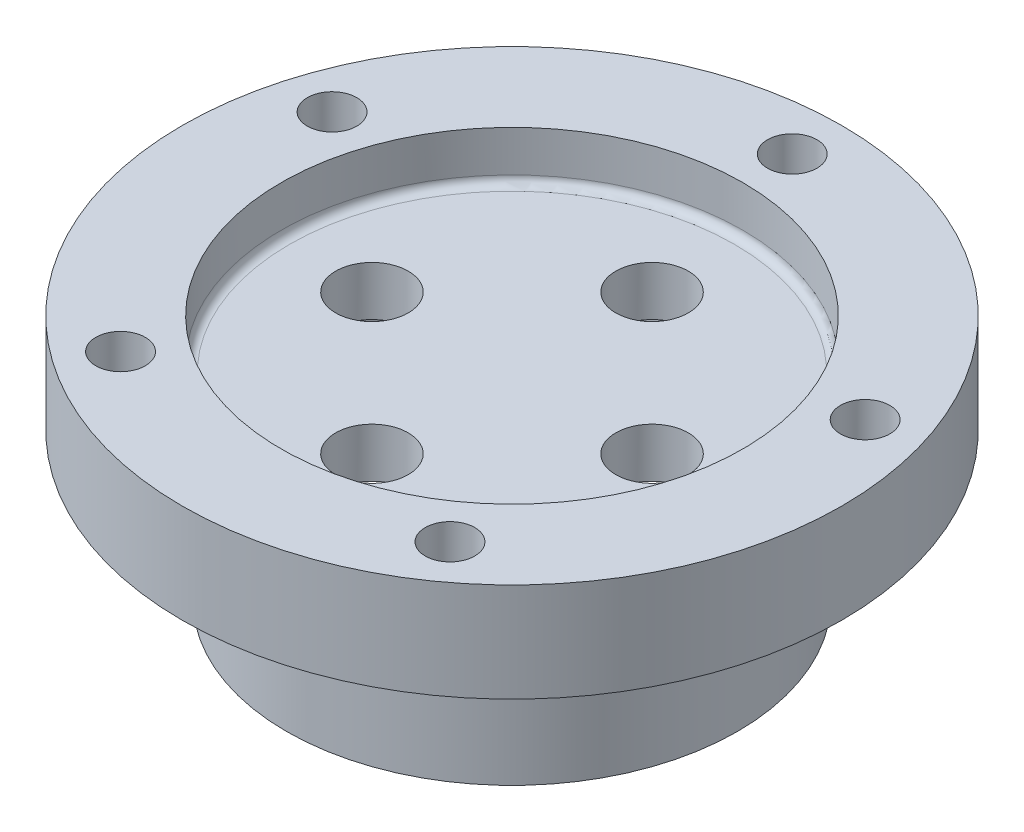
SolidWorks part; units mm, degrees
material "ASTM A36 Steel"
ref_plane "Front Plane" through (0, 0, 0) normal (0, 0, 1) x (1, 0, 0)
ref_plane "Top Plane" through (0, 0, 0) normal (0, 1, 0) x (1, 0, 0)
ref_plane "Right Plane" through (0, 0, 0) normal (1, 0, 0) x (0, 0, -1)
sketch "Sketch1" plane through (0, 0, 0) normal (0, 0, 1) x (1, 0, 0)
  line L0 (18.542, -14.2875) -> (18.542, 0)
  line L1 (55, 0) -> (-55, 0) construction
  line L2 (18.542, 0) -> (0, 0)
  line L3 (0, 0) -> (0, 20.0604) construction
  line L4 (0, 4.7625) -> (22.225, 4.7625)
  line L5 (22.225, 4.7625) -> (22.225, 9.525)
  line L9 (31.75, 9.525) -> (31.75, 0)
  line L10 (31.75, 0) -> (21.717, 0)
  line L11 (21.717, 0) -> (21.717, -14.2875)
  line L12 (21.717, -14.2875) -> (18.542, -14.2875)
  line L14 (22.225, 9.525) -> (31.75, 9.525)
  line L15 (0, 4.7625) -> (0, 0)
  dimension "D2" = 37.084
  dimension "D3" = 63.5
  dimension "D4" = 14.2875
  dimension "D5" = 14.2875
  dimension "D9" = 9.525
  dimension "D10" = 3.175
  dimension "D11" = 4.7625
  dimension "D12" = 44.45
revolve "Revolve1" add sketch "Sketch1" angle 360 about L3
sketch "Sketch2" plane through (0, 4.7625, 0) normal (0, 1, 0) x (1, 0, 0)
  line L0 (13.4874, 0) -> (-13.4874, 0)
  line L1 (0, -13.4874) -> (0, 13.4874)
  circle A0 centre (-13.4874, 0) radius 3.4925
  circle A1 centre (0, 13.4874) radius 3.4925
  circle A2 centre (13.4874, 0) radius 3.4925
  circle A3 centre (0, -13.4874) radius 3.4925
  point P8 (0, 0)
  dimension "D2" = 6.985
  dimension "D1" = 13.4874
extrude "Cut-Extrude1" cut sketch "Sketch2" against normal through all contours A0 | A3 | A2 | A1
sketch "Sketch3" plane through (0, 9.525, 0) normal (0, 1, 0) x (1, 0, 0)
  line L0 (0, 31.75) -> (0, 22.225) construction
  line L2 (0, -13.0969) -> (0, 13.0969) construction
  line L3 (-13.0969, 0) -> (13.0969, 0) construction
  circle A0 centre (0, 0) radius 31.75 construction
  circle A2 centre (0, 26.9875) radius 2.3813
  circle A3 centre (0, 0) radius 22.225 construction
  circle A4 centre (0, 0) radius 31.75
  circle A5 centre (0, 0) radius 22.225
  dimension "D1" = 4.7625
  dimension "D2" = 26.9875
extrude "Cut-Extrude2" cut sketch "Sketch3" against normal through all contours A2 | L0 A2 region at (1.0106, 9.525, -26.9875) region at (-1.0106, 9.525, -26.9875)
ref_axis "Axis1" through (0, 14.7638, 0) along (0, -1, 0)
pattern_circular "CirPattern1" count 5 over 360 about axis through (0, 14.7638, 0) along (0, -1, 0) of "Cut-Extrude2"
fillet "Fillet1" radius 0.7937 2 edges at (0, 4.7625, -22.225) (0, 0, -18.542)
